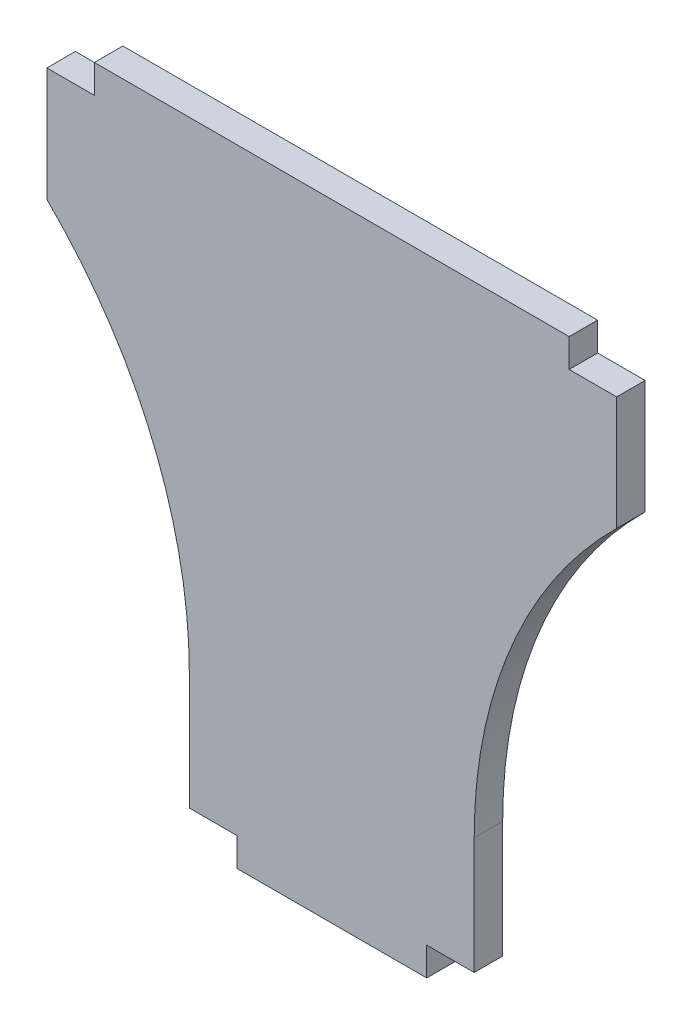
SolidWorks part; units mm, degrees
material "Acrylic (Medium-high impact)"
ref_plane "Plano frontal" through (0, 0, 0) normal (0, 0, 1) x (1, 0, 0)
ref_plane "Plano superior" through (0, 0, 0) normal (0, 1, 0) x (1, 0, 0)
ref_plane "Plano direito" through (0, 0, 0) normal (1, 0, 0) x (0, 0, -1)
sketch "Sketch2" plane through (0, 0, 0) normal (0, 0, 1) x (1, 0, 0)
  line L0 (15, 24) -> (30, 24)
  line L1 (10, -24) -> (15, -24)
  line L2 (-15, 24) -> (-15, -24)
  line L3 (-15, -24) -> (-10, -24)
  line L4 (15, 24) -> (15, -24)
  line L5 (-15, 24) -> (15, -24) construction
  line L6 (-15, -24) -> (15, 24) construction
  line L7 (-30, 36) -> (-25, 36)
  line L8 (-30, 36) -> (-30, 24)
  line L9 (-30, 24) -> (-15, 24)
  line L10 (30, 36) -> (30, 24)
  line L11 (-25, 39) -> (25, 39)
  line L12 (-25, 39) -> (-25, 36)
  line L14 (25, 39) -> (25, 36)
  line L16 (-10, -24) -> (-10, -27)
  line L17 (-10, -27) -> (10, -27)
  line L18 (10, -24) -> (10, -27)
  line L19 (25, 36) -> (30, 36)
  point P0 (0, 0)
  point P20 (0, 39)
  point P21 (0, -27)
  dimension "D1" = 60
  dimension "D2" = 3
  dimension "D3" = 3
  dimension "D4" = 30
  dimension "D5" = 20
  dimension "D6" = 60
  dimension "D7" = 12
  dimension "D8" = 50
extrude "Boss-Extrude1" add sketch "Sketch2" along normal mid plane 3
fillet "Fillet1" radius 50 2 edges at (-15, 24, 0) (15, 24, 0)
